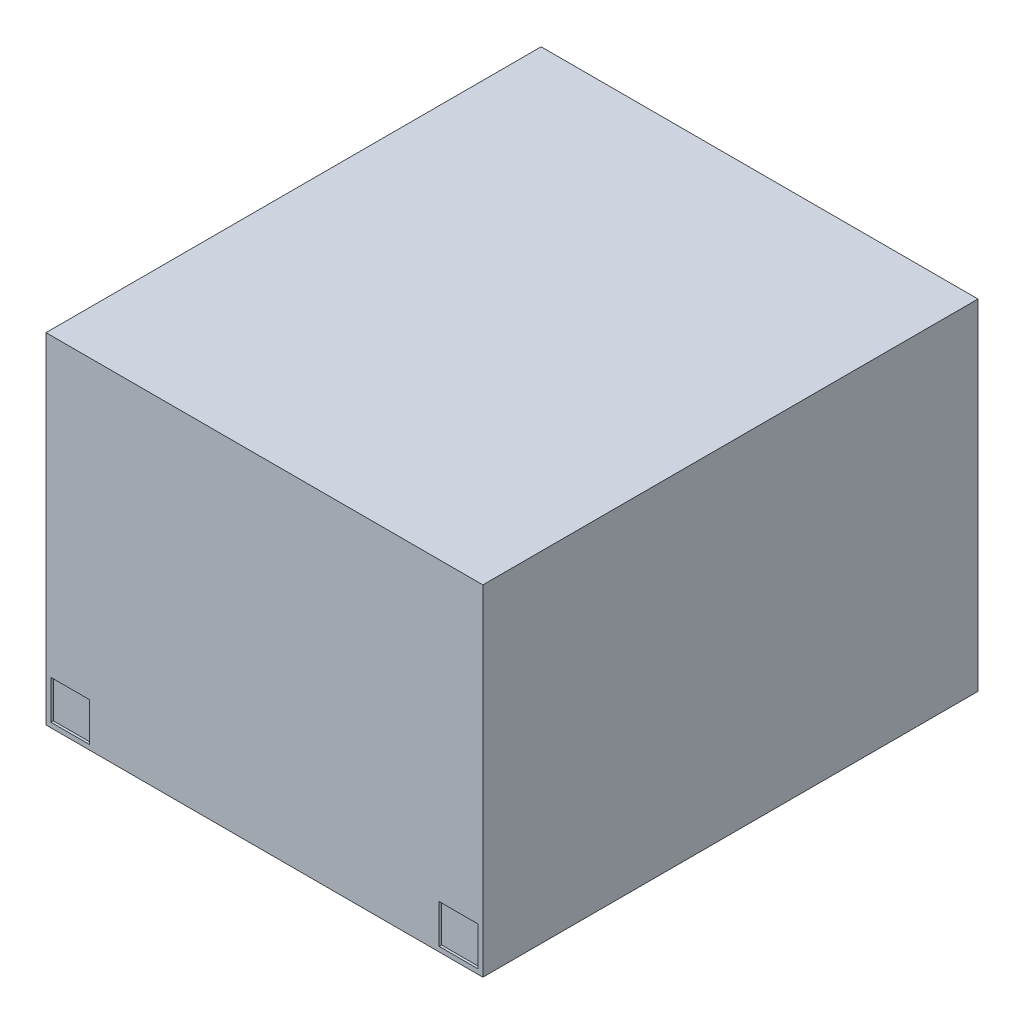
SolidWorks part; units mm, degrees
ref_plane "前基準面" through (0, 0, 0) normal (0, 0, 1) x (1, 0, 0)
ref_plane "上基準面" through (0, 0, 0) normal (0, 1, 0) x (1, 0, 0)
ref_plane "右基準面" through (0, 0, 0) normal (1, 0, 0) x (0, 0, -1)
sketch "草圖1" plane through (0, 0, 0) normal (0, 0, 1) x (1, 0, 0)
  line L1 (-45, -35) -> (45, -35)
  line L2 (-45, -35) -> (-45, 35)
  line L3 (-45, 35) -> (45, 35)
  line L4 (45, -35) -> (45, 35)
  line L5 (-45, -35) -> (45, 35) construction
  line L6 (-45, 35) -> (45, -35) construction
  point P0 (0, 0)
  dimension "D1" = 90
  dimension "D2" = 70
extrude "填料-伸長1" add sketch "草圖1" along normal blind 102
sketch "草圖2" plane through (0, 0, 102) normal (0, 0, 1) x (1, 0, 0)
  line L0 (-45, 35) -> (-45, -35) construction
  line L1 (-44, -34) -> (-36, -34)
  line L2 (-44, -34) -> (-44, -26)
  line L3 (-44, -26) -> (-36, -26)
  line L4 (-36, -34) -> (-36, -26)
  line L5 (-44, -34) -> (-36, -26) construction
  line L6 (-44, -26) -> (-36, -34) construction
  line L7 (-45, -35) -> (45, -35) construction
  point P0 (-40, -30)
  dimension "D1" = 8
  dimension "D2" = 8
  dimension "D3" = 1
  dimension "D4" = 1
extrude "除料-伸長1" cut sketch "草圖2" against normal blind 0.5
mirror "鏡射1" about plane through (0, 0, 0) normal (1, 0, 0) of "除料-伸長1"
